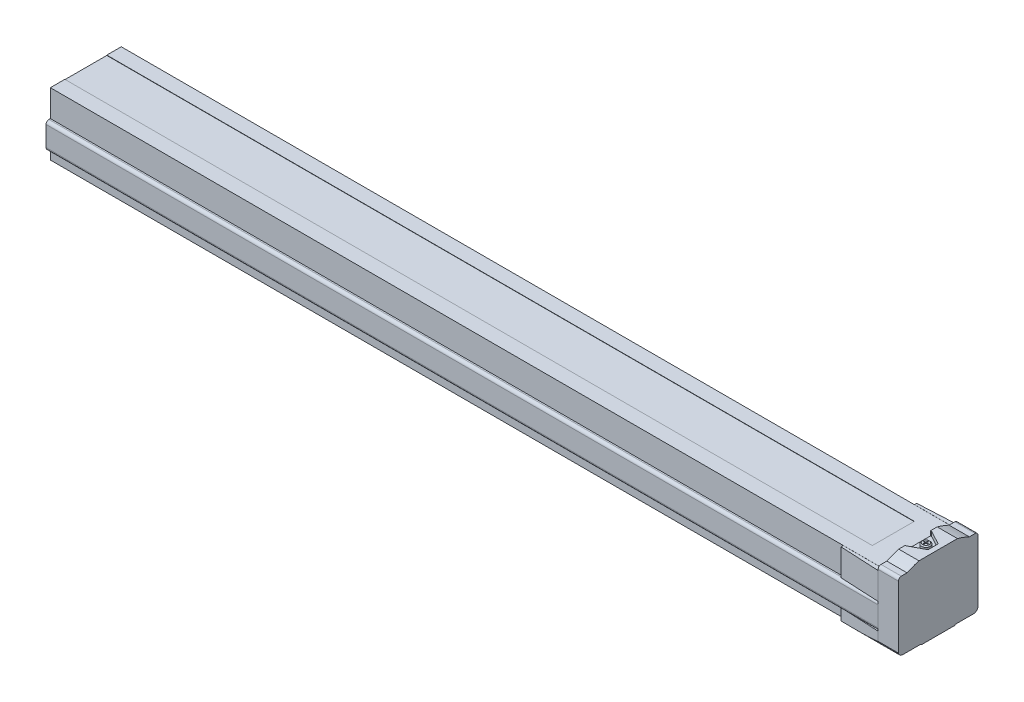
SolidWorks part; units mm, degrees
ref_plane "Front" through (0, 0, 0) normal (0, 0, 1) x (1, 0, 0)
ref_plane "Top" through (0, 0, 0) normal (0, 1, 0) x (1, 0, 0)
ref_plane "Right" through (0, 0, 0) normal (1, 0, 0) x (0, 0, -1)
ref_plane "Plane1" through (0, 0, 0) normal (1, 0, 0) x (0, 0, -1)
sketch "Sketch1" plane through (0, 0, 0) normal (1, 0, 0) x (0, 0, -1)
  line L0 (-28.5, 46) -> (-28.5, 2.9714)
  line L1 (-28.5, 2.9714) -> (-27.5, 2.9714)
  line L2 (-27.5, 2.9714) -> (-27.3284, 2.5)
  line L3 (-24.5, 0.5) -> (-12, 0.5)
  line L4 (-12, 0.5) -> (-11.5, 0)
  line L5 (-11.5, 0) -> (11.5, 0)
  line L6 (11.5, 0) -> (12, 0.5)
  line L7 (12, 0.5) -> (24.5, 0.5)
  line L8 (27.3284, 2.5) -> (27.5, 2.9714)
  line L9 (27.5, 2.9714) -> (28.5, 2.9714)
  line L10 (28.5, 2.9714) -> (28.5, 46)
  line L11 (28.5, 46) -> (27.5, 46)
  line L12 (25.5, 48) -> (21.524, 48)
  line L13 (13.2951, 51.07) -> (-13.2951, 51.07)
  line L14 (-21.524, 48) -> (-25.5, 48)
  line L15 (-27.5, 46) -> (-28.5, 46)
  arc A0 (-27.3284, 2.5) -> (-24.5, 0.5) centre (-24.5, 3.5) ccw
  arc A1 (24.5, 0.5) -> (27.3284, 2.5) centre (24.5, 3.5) ccw
  arc A2 (27.5, 46) -> (25.5, 48) centre (25.5, 46) ccw
  arc A3 (21.524, 48) -> (13.2951, 51.07) centre (0, 2.87) ccw
  arc A4 (-13.2951, 51.07) -> (-21.524, 48) centre (0, 2.87) ccw
  arc A5 (-25.5, 48) -> (-27.5, 46) centre (-25.5, 46) ccw
extrude "Boss-Extrude1" add sketch "Sketch1" along normal blind 930
ref_plane "Plane2" through (916, 0, 0) normal (1, 0, 0) x (0, 0, -1)
sketch "Sketch2" plane through (916, 0, 0) normal (1, 0, 0) x (0, 0, -1)
  line L0 (-92.8608, 99.7478) -> (-92.8608, -68.8998)
  line L1 (-92.8608, -68.8998) -> (111.9255, -68.8998)
  line L2 (111.9255, -68.8998) -> (111.9255, 99.7478)
  line L3 (111.9255, 99.7478) -> (-92.8608, 99.7478)
  line L4 (-27.5, 24.8) -> (-27.5, 11)
  line L5 (-25.5, 9) -> (-24.5, 9)
  line L6 (-24.5, 9) -> (-24.5, 2)
  line L7 (-24.5, 2) -> (-22.5, 0)
  line L8 (-22.5, 0) -> (22.5, 0)
  line L9 (22.5, 0) -> (24.5, 2)
  line L10 (24.5, 2) -> (24.5, 9)
  line L11 (24.5, 9) -> (25.5, 9)
  line L12 (27.5, 11) -> (27.5, 24.8)
  line L13 (25.5, 26.8) -> (24.5, 26.8)
  line L14 (24.5, 26.8) -> (24.5, 45.3)
  line L15 (24.5, 45.3) -> (-24.5, 45.3)
  line L16 (-24.5, 45.3) -> (-24.5, 26.8)
  line L17 (-24.5, 26.8) -> (-25.5, 26.8)
  arc A0 (-27.5, 11) -> (-25.5, 9) centre (-25.5, 11) ccw
  arc A1 (25.5, 9) -> (27.5, 11) centre (25.5, 11) ccw
  arc A2 (27.5, 24.8) -> (25.5, 26.8) centre (25.5, 24.8) ccw
  arc A3 (-25.5, 26.8) -> (-27.5, 24.8) centre (-25.5, 24.8) ccw
extrude "Cut-Extrude1" cut sketch "Sketch2" against normal blind 909.5
ref_plane "Plane3" through (0, 0, 0) normal (1, 0, 0) x (0, 0, -1)
sketch "Sketch3" plane through (0, 0, 0) normal (1, 0, 0) x (0, 0, -1)
  line L0 (-200, 100) -> (-200, -100)
  line L1 (-200, -100) -> (200, -100)
  line L2 (200, -100) -> (200, 100)
  line L3 (200, 100) -> (-200, 100)
  line L4 (-27.5, 46) -> (-27.5, 2.9714)
  line L5 (-27.5, 2.9714) -> (-27.3284, 2.5)
  line L6 (-24.5, 0.5) -> (-12, 0.5)
  line L7 (-12, 0.5) -> (-11.5, 0)
  line L8 (-11.5, 0) -> (11.5, 0)
  line L9 (11.5, 0) -> (12, 0.5)
  line L10 (12, 0.5) -> (24.5, 0.5)
  line L11 (27.3284, 2.5) -> (27.5, 2.9714)
  line L12 (27.5, 2.9714) -> (27.5, 46)
  line L13 (25.5, 48) -> (21.524, 48)
  line L14 (13.2951, 51.07) -> (-13.2951, 51.07)
  line L15 (-21.524, 48) -> (-25.5, 48)
  arc A0 (-27.3284, 2.5) -> (-24.5, 0.5) centre (-24.5, 3.5) ccw
  arc A1 (24.5, 0.5) -> (27.3284, 2.5) centre (24.5, 3.5) ccw
  arc A2 (27.5, 46) -> (25.5, 48) centre (25.5, 46) ccw
  arc A3 (21.524, 48) -> (13.2951, 51.07) centre (0, 2.87) ccw
  arc A4 (-13.2951, 51.07) -> (-21.524, 48) centre (0, 2.87) ccw
  arc A5 (-25.5, 48) -> (-27.5, 46) centre (-25.5, 46) ccw
extrude "Cut-Extrude2" cut sketch "Sketch3" along normal blind 930
ref_plane "Plane4" through (0, 0, 0) normal (1, 0, 0) x (0, 0, -1)
sketch "Sketch4" plane through (0, 0, 0) normal (1, 0, 0) x (0, 0, -1)
  line L0 (-24.5, 30) -> (24.5, 30)
  line L1 (24.5, 30) -> (24.5, 45.3)
  line L2 (24.5, 45.3) -> (24.45, 45.3)
  line L3 (24.45, 45.3) -> (24.5, 45.35)
  line L4 (24.5, 45.35) -> (24.5, 48)
  line L5 (24.5, 48) -> (24, 48)
  line L6 (24, 48) -> (22.2857, 52.7101)
  line L7 (17.5872, 56) -> (-17.0842, 56)
  line L8 (-21.6157, 53.1131) -> (-24, 48)
  line L9 (-24, 48) -> (-24.5, 48)
  line L10 (-24.5, 48) -> (-24.5, 45.35)
  line L11 (-24.5, 45.35) -> (-24.45, 45.3)
  line L12 (-24.45, 45.3) -> (-24.5, 45.3)
  line L13 (-24.5, 45.3) -> (-24.5, 30)
  arc A0 (22.2857, 52.7101) -> (17.5872, 56) centre (17.5872, 51) ccw
  arc A1 (-17.0842, 56) -> (-21.6157, 53.1131) centre (-17.0842, 51) ccw
extrude "Boss-Extrude2" add sketch "Sketch4" along normal blind 127.35
ref_plane "Plane5" through (0, 0, 0) normal (0, 0, 1) x (1, 0, 0)
sketch "Sketch5" plane through (0, 0, 0) normal (0, 0, 1) x (1, 0, 0)
  line L0 (97.35, 71.9713) -> (150, 71.9713)
  line L1 (150, 71.9713) -> (150, 45.3)
  line L2 (150, 45.3) -> (127.35, 45.3)
  line L3 (127.35, 45.3) -> (127.35, 45.79)
  line L4 (126.9005, 47.0533) -> (120.2965, 55.1583)
  line L5 (116.4203, 57) -> (97.35, 57)
  line L6 (97.35, 57) -> (97.35, 71.9713)
  line L7 (97.35, 57) -> (97.35, 71.9713) construction
  arc A0 (127.35, 45.79) -> (126.9005, 47.0533) centre (125.35, 45.79) ccw
  arc A1 (120.2965, 55.1583) -> (116.4203, 57) centre (116.4203, 52) ccw
revolve "Cut-Revolve1" cut sketch "Sketch5" angle 75 about L7 other way angle 75 reverse direction yes
ref_plane "Plane6" through (0, 48, 0) normal (0, 1, 0) x (-1, 0, 0)
sketch "Sketch6" plane through (0, 48, 0) normal (0, 1, 0) x (-1, 0, 0)
  line L0 (-916, 8.7) -> (-916.7202, 8.7)
  line L1 (-916.7202, 8.7) -> (-926.5, 3.5)
  line L2 (-926.5, 3.5) -> (-926.5, -3.5)
  line L3 (-926.5, -3.5) -> (-916.7202, -8.7)
  line L4 (-916.7202, -8.7) -> (-916, -8.7)
  line L5 (-916, -8.7) -> (-916, 8.7)
extrude "Cut-Extrude4" cut sketch "Sketch6" along normal blind 20
ref_plane "Plane7" through (0, 0, 0) normal (0, 0, 1) x (1, 0, 0)
sketch "Sketch7" plane through (0, 0, 0) normal (0, 0, 1) x (1, 0, 0)
  line L0 (921.5, 48) -> (918.5, 48)
  line L1 (918.5, 48) -> (918.5, 50.2929)
  line L2 (918.5, 50.2929) -> (919.2071, 51)
  line L3 (919.2071, 51) -> (921.5, 51)
  line L4 (921.5, 51) -> (921.5, 48)
  line L5 (921.5, 51) -> (921.5, 48) construction
revolve "Revolve1" add sketch "Sketch7" angle 360 about L5 reverse direction yes
ref_plane "Plane8" through (0, 51, 0) normal (0, 1, 0) x (-1, 0, 0)
sketch "Sketch8" plane through (0, 51, 0) normal (0, 1, 0) x (-1, 0, 0)
  line L0 (-923.0716, -0.3) -> (-921.8, -0.3)
  line L1 (-921.8, -0.3) -> (-921.8, -1.5716)
  line L2 (-921.2, -1.5716) -> (-921.2, -0.3)
  line L3 (-921.2, -0.3) -> (-919.9284, -0.3)
  line L4 (-919.9284, 0.3) -> (-921.2, 0.3)
  line L5 (-921.2, 0.3) -> (-921.2, 1.5716)
  line L6 (-921.8, 1.5716) -> (-921.8, 0.3)
  line L7 (-921.8, 0.3) -> (-923.0716, 0.3)
  arc A0 (-923.0716, 0.3) -> (-923.0716, -0.3) centre (-921.5, 0) ccw
  arc A1 (-921.8, -1.5716) -> (-921.2, -1.5716) centre (-921.5, 0) ccw
  arc A2 (-919.9284, -0.3) -> (-919.9284, 0.3) centre (-921.5, 0) ccw
  arc A3 (-921.2, 1.5716) -> (-921.8, 1.5716) centre (-921.5, 0) ccw
extrude "Cut-Extrude5" cut sketch "Sketch8" against normal blind 1
ref_plane "Plane9" through (0, 0, 0) normal (0, 0, 1) x (1, 0, 0)
sketch "Sketch9" plane through (0, 0, 0) normal (0, 0, 1) x (1, 0, 0)
  line L0 (-50, 0.5) -> (-50, 0)
  line L1 (-50, 0) -> (79, 0)
  line L2 (79, 0) -> (78.5, 0.5)
  line L3 (78.5, 0.5) -> (-50, 0.5)
extrude "Cut-Extrude6" cut sketch "Sketch9" against normal blind 20 and the other way blind 20
ref_plane "Plane10" through (0, 0, 0) normal (0, 1, 0) x (-1, 0, 0)
sketch "Sketch10" plane through (0, 0, 0) normal (0, 1, 0) x (-1, 0, 0)
  line L0 (-625.5, 2) -> (-627.5, 2)
  line L1 (-627.5, -2) -> (-625.5, -2)
  arc A0 (-625.5, -2) -> (-625.5, 2) centre (-625.5, 0) ccw
  arc A1 (-627.5, 2) -> (-627.5, -2) centre (-627.5, 0) ccw
extrude "Cut-Extrude7" cut sketch "Sketch10" along normal blind 6
ref_plane "Plane11" through (0, 26.8, 0) normal (0, 1, 0) x (-1, 0, 0)
sketch "Sketch11" plane through (0, 26.8, 0) normal (0, 1, 0) x (-1, 0, 0)
  line L0 (0, 27.5) -> (-6, 27.5)
  line L1 (-6, 27.5) -> (-34, 26.1)
  line L2 (-34, 26.1) -> (-34, -26.1)
  line L3 (-34, -26.1) -> (-6, -27.5)
  line L4 (-6, -27.5) -> (0, -27.5)
  line L5 (0, -27.5) -> (0, 27.5)
extrude "Boss-Extrude8" add sketch "Sketch11" along normal blind 21.2
ref_plane "Plane12" through (0, 0, 0) normal (0, 0, 1) x (1, 0, 0)
sketch "Sketch12" plane through (0, 0, 0) normal (0, 0, 1) x (1, 0, 0)
  line L0 (-20, -15) -> (15, -15)
  line L1 (15, -15) -> (15, 0)
  line L2 (15, 0) -> (5.5878, 0)
  line L3 (0.6068, 4.5642) -> (0, 11.5)
  line L4 (0, 11.5) -> (0, 40.45)
  line L5 (0, 40.45) -> (2.1897, 52.8682)
  line L6 (7.1137, 57) -> (15, 57)
  line L7 (15, 57) -> (15, 60)
  line L8 (15, 60) -> (-20, 60)
  line L9 (-20, 60) -> (-20, -15)
  arc A0 (5.5878, 0) -> (0.6068, 4.5642) centre (5.5878, 5) cw
  arc A1 (2.1897, 52.8682) -> (7.1137, 57) centre (7.1137, 52) cw
extrude "Cut-Extrude9" cut sketch "Sketch12" against normal blind 30 and the other way blind 30
ref_plane "Plane13" through (0, 0, 0) normal (1, 0, 0) x (0, 0, -1)
sketch "Sketch13" plane through (0, 0, 0) normal (1, 0, 0) x (0, 0, -1)
  line L0 (-10, 46.95) -> (-10, 42.95)
  line L1 (-5, 37.95) -> (5, 37.95)
  line L2 (10, 42.95) -> (10, 46.95)
  line L3 (9, 47.95) -> (-9, 47.95)
  arc A0 (-10, 42.95) -> (-5, 37.95) centre (-5, 42.95) ccw
  arc A1 (5, 37.95) -> (10, 42.95) centre (5, 42.95) ccw
  arc A2 (10, 46.95) -> (9, 47.95) centre (9, 46.95) ccw
  arc A3 (-9, 47.95) -> (-10, 46.95) centre (-9, 46.95) ccw
extrude "Cut-Extrude10" cut sketch "Sketch13" against normal blind 2 and the other way blind 2
ref_plane "Plane14" through (2, 0, 0) normal (1, 0, 0) x (0, 0, -1)
sketch "Sketch14" plane through (2, 0, 0) normal (1, 0, 0) x (0, 0, -1)
  circle A0 centre (-3.5, 43.7) radius 3.25
extrude "Boss-Extrude3" add sketch "Sketch14" against normal blind 20
ref_plane "Plane15" through (2, 0, 0) normal (1, 0, 0) x (0, 0, -1)
sketch "Sketch15" plane through (2, 0, 0) normal (1, 0, 0) x (0, 0, -1)
  circle A0 centre (3.5, 43.7) radius 3.25
extrude "Boss-Extrude4" add sketch "Sketch15" against normal blind 20
ref_plane "Plane16" through (0, 9, 0) normal (0, 1, 0) x (-1, 0, 0)
sketch "Sketch16" plane through (0, 9, 0) normal (0, 1, 0) x (-1, 0, 0)
  line L0 (0, 27.5) -> (-6, 27.5)
  line L1 (-6, 27.5) -> (-34, 26.1)
  line L2 (-34, 26.1) -> (-34, -26.1)
  line L3 (-34, -26.1) -> (-6, -27.5)
  line L4 (-6, -27.5) -> (0, -27.5)
  line L5 (0, -27.5) -> (0, 27.5)
extrude "Boss-Extrude5" add sketch "Sketch16" against normal blind 8.56
ref_plane "Plane17" through (0, 0, 0) normal (1, 0, 0) x (0, 0, -1)
sketch "Sketch17" plane through (0, 0, 0) normal (1, 0, 0) x (0, 0, -1)
  line L0 (-109.3927, 115.6666) -> (-109.3927, -79.3609)
  line L1 (-109.3927, -79.3609) -> (125.9854, -79.3609)
  line L2 (125.9854, -79.3609) -> (125.9854, 115.6666)
  line L3 (125.9854, 115.6666) -> (-109.3927, 115.6666)
  line L4 (-27.5, 46) -> (-27.5, 2.9714)
  line L5 (-27.5, 2.9714) -> (-27.3284, 2.5)
  line L6 (-24.5, 0.5) -> (24.5, 0.5)
  line L7 (27.3284, 2.5) -> (27.5, 2.9714)
  line L8 (27.5, 2.9714) -> (27.5, 46)
  line L9 (25.5, 48) -> (24, 48)
  line L10 (24, 48) -> (24, 65)
  line L11 (24, 65) -> (-24, 65)
  line L12 (-24, 65) -> (-24, 48)
  line L13 (-24, 48) -> (-25.5, 48)
  arc A0 (-27.3284, 2.5) -> (-24.5, 0.5) centre (-24.5, 3.5) ccw
  arc A1 (24.5, 0.5) -> (27.3284, 2.5) centre (24.5, 3.5) ccw
  arc A2 (27.5, 46) -> (25.5, 48) centre (25.5, 46) ccw
  arc A3 (-25.5, 48) -> (-27.5, 46) centre (-25.5, 46) ccw
extrude "Cut-Extrude14" cut sketch "Sketch17" along normal blind 40
ref_plane "Plane18" through (0, 26.8, 0) normal (0, 1, 0) x (-1, 0, 0)
sketch "Sketch18" plane through (0, 26.8, 0) normal (0, 1, 0) x (-1, 0, 0)
  line L0 (-889, 26.1) -> (-917, 27.5)
  line L1 (-917, 27.5) -> (-923, 27.5)
  line L2 (-923, 27.5) -> (-923, -27.5)
  line L3 (-923, -27.5) -> (-917, -27.5)
  line L4 (-917, -27.5) -> (-889, -26.1)
  line L5 (-889, -26.1) -> (-889, 26.1)
extrude "Boss-Extrude6" add sketch "Sketch18" along normal blind 18.5
ref_plane "Plane19" through (0, 9, 0) normal (0, 1, 0) x (-1, 0, 0)
sketch "Sketch19" plane through (0, 9, 0) normal (0, 1, 0) x (-1, 0, 0)
  line L0 (-889, 26.1) -> (-917, 27.5)
  line L1 (-917, 27.5) -> (-930, 27.5)
  line L2 (-930, 27.5) -> (-930, -27.5)
  line L3 (-930, -27.5) -> (-917, -27.5)
  line L4 (-917, -27.5) -> (-889, -26.1)
  line L5 (-889, -26.1) -> (-889, 26.1)
extrude "Boss-Extrude7" add sketch "Sketch19" against normal blind 8.56
ref_plane "Plane20" through (930, 0, 0) normal (1, 0, 0) x (0, 0, -1)
sketch "Sketch20" plane through (930, 0, 0) normal (1, 0, 0) x (0, 0, -1)
  line L0 (-109.3927, 115.6666) -> (-109.3927, -79.3609)
  line L1 (-109.3927, -79.3609) -> (125.9854, -79.3609)
  line L2 (125.9854, -79.3609) -> (125.9854, 115.6666)
  line L3 (125.9854, 115.6666) -> (-109.3927, 115.6666)
  line L4 (-27.5, 46) -> (-27.5, 2.9714)
  line L5 (-27.5, 2.9714) -> (-27.3284, 2.5)
  line L6 (-24.5, 0.5) -> (-12, 0.5)
  line L7 (-12, 0.5) -> (-11.5, 0)
  line L8 (-11.5, 0) -> (11.5, 0)
  line L9 (11.5, 0) -> (12, 0.5)
  line L10 (12, 0.5) -> (24.5, 0.5)
  line L11 (27.3284, 2.5) -> (27.5, 2.9714)
  line L12 (27.5, 2.9714) -> (27.5, 46)
  line L13 (25.5, 48) -> (24, 48)
  line L14 (24, 48) -> (24, 65)
  line L15 (24, 65) -> (-24, 65)
  line L16 (-24, 65) -> (-24, 48)
  line L17 (-24, 48) -> (-25.5, 48)
  arc A0 (-27.3284, 2.5) -> (-24.5, 0.5) centre (-24.5, 3.5) ccw
  arc A1 (24.5, 0.5) -> (27.3284, 2.5) centre (24.5, 3.5) ccw
  arc A2 (27.5, 46) -> (25.5, 48) centre (25.5, 46) ccw
  arc A3 (-25.5, 48) -> (-27.5, 46) centre (-25.5, 46) ccw
extrude "Cut-Extrude17" cut sketch "Sketch20" against normal blind 50
ref_plane "Plane21" through (0, 0, 0) normal (0, 0, 1) x (1, 0, 0)
sketch "Sketch21" plane through (0, 0, 0) normal (0, 0, 1) x (1, 0, 0)
  line L0 (111, 60.8331) -> (116, 60.8331)
  line L1 (116, 60.8331) -> (116, 55.5)
  line L2 (116, 55.5) -> (115.7, 55.8)
  line L3 (115.7, 55.8) -> (111, 55.8)
  line L4 (111, 55.8) -> (111, 60.8331)
  line L5 (111, 55.8) -> (111, 60.8331) construction
revolve "Cut-Revolve2" cut sketch "Sketch21" angle 360 about L5 reverse direction yes
ref_plane "Plane22" through (0, 55.8, 0) normal (0, 1, 0) x (-1, 0, 0)
sketch "Sketch22" plane through (0, 55.8, 0) normal (0, 1, 0) x (-1, 0, 0)
  line L0 (-108.042, 0.5) -> (-110.5, 0.5)
  line L1 (-110.5, 0.5) -> (-110.5, 2.958)
  line L2 (-111.5, 2.958) -> (-111.5, 0.5)
  line L3 (-111.5, 0.5) -> (-113.958, 0.5)
  line L4 (-113.958, -0.5) -> (-111.5, -0.5)
  line L5 (-111.5, -0.5) -> (-111.5, -2.958)
  line L6 (-110.5, -2.958) -> (-110.5, -0.5)
  line L7 (-110.5, -0.5) -> (-108.042, -0.5)
  arc A0 (-108.042, -0.5) -> (-108.042, 0.5) centre (-111, 0) ccw
  arc A1 (-110.5, 2.958) -> (-111.5, 2.958) centre (-111, 0) ccw
  arc A2 (-113.958, 0.5) -> (-113.958, -0.5) centre (-111, 0) ccw
  arc A3 (-111.5, -2.958) -> (-110.5, -2.958) centre (-111, 0) ccw
extrude "Cut-Extrude18" cut sketch "Sketch22" against normal blind 3
ref_plane "Plane23" through (0, 45.3, 0) normal (0, 1, 0) x (-1, 0, 0)
sketch "Sketch23" plane through (0, 45.3, 0) normal (0, 1, 0) x (-1, 0, 0)
  line L0 (-157, 14.5) -> (-899, 14.5)
  line L1 (-899, 14.5) -> (-899, -14.5)
  line L2 (-899, -14.5) -> (-157, -14.5)
  line L3 (-157, -14.5) -> (-157, 14.5)
extrude "Cut-Extrude19" cut sketch "Sketch23" against normal blind 0.2
ref_plane "Plane24" through (0, 0, 0) normal (0, 0, 1) x (1, 0, 0)
sketch "Sketch24" plane through (0, 0, 0) normal (0, 0, 1) x (1, 0, 0)
  line L0 (126.5, 0) -> (124.5, 0)
  line L1 (124.5, 0) -> (124.5, 6)
  line L2 (124.5, 6) -> (126.5, 7.1547)
  line L3 (126.5, 7.1547) -> (126.5, 0)
  line L4 (126.5, 7.1547) -> (126.5, 0) construction
revolve "Cut-Revolve3" cut sketch "Sketch24" angle 360 about L4 reverse direction yes
ref_plane "Plane25" through (101.5, 0, 0) normal (1, 0, 0) x (0, 0, -1)
sketch "Sketch25" plane through (101.5, 0, 0) normal (1, 0, 0) x (0, 0, -1)
  line L0 (0, 11.0194) -> (2.4585, 9.6)
  line L1 (2.4585, 9.6) -> (2.4585, 0.5415)
  line L2 (2.4585, 0.5415) -> (3, 0)
  line L3 (3, 0) -> (0, 0)
  line L4 (0, 0) -> (0, 11.0194)
  line L5 (0, 0) -> (0, 11.0194) construction
revolve "Cut-Revolve4" cut sketch "Sketch25" angle 360 about L5 reverse direction yes
ref_plane "Plane26" through (901.5, 0, 0) normal (1, 0, 0) x (0, 0, -1)
sketch "Sketch26" plane through (901.5, 0, 0) normal (1, 0, 0) x (0, 0, -1)
  line L0 (0, 11.0194) -> (2.4585, 9.6)
  line L1 (2.4585, 9.6) -> (2.4585, 0.5415)
  line L2 (2.4585, 0.5415) -> (3, 0)
  line L3 (3, 0) -> (0, 0)
  line L4 (0, 0) -> (0, 11.0194)
  line L5 (0, 0) -> (0, 11.0194) construction
revolve "Cut-Revolve5" cut sketch "Sketch26" angle 360 about L5 reverse direction yes
ref_plane "Plane27" through (851.5, 0, 0) normal (1, 0, 0) x (0, 0, -1)
sketch "Sketch27" plane through (851.5, 0, 0) normal (1, 0, 0) x (0, 0, -1)
  line L0 (0, 11.0194) -> (2.4585, 9.6)
  line L1 (2.4585, 9.6) -> (2.4585, 0.5415)
  line L2 (2.4585, 0.5415) -> (3, 0)
  line L3 (3, 0) -> (0, 0)
  line L4 (0, 0) -> (0, 11.0194)
  line L5 (0, 0) -> (0, 11.0194) construction
revolve "Cut-Revolve6" cut sketch "Sketch27" angle 360 about L5 reverse direction yes
ref_plane "Plane28" through (801.5, 0, 0) normal (1, 0, 0) x (0, 0, -1)
sketch "Sketch28" plane through (801.5, 0, 0) normal (1, 0, 0) x (0, 0, -1)
  line L0 (0, 11.0194) -> (2.4585, 9.6)
  line L1 (2.4585, 9.6) -> (2.4585, 0.5415)
  line L2 (2.4585, 0.5415) -> (3, 0)
  line L3 (3, 0) -> (0, 0)
  line L4 (0, 0) -> (0, 11.0194)
  line L5 (0, 0) -> (0, 11.0194) construction
revolve "Cut-Revolve7" cut sketch "Sketch28" angle 360 about L5 reverse direction yes
ref_plane "Plane29" through (751.5, 0, 0) normal (1, 0, 0) x (0, 0, -1)
sketch "Sketch29" plane through (751.5, 0, 0) normal (1, 0, 0) x (0, 0, -1)
  line L0 (0, 11.0194) -> (2.4585, 9.6)
  line L1 (2.4585, 9.6) -> (2.4585, 0.5415)
  line L2 (2.4585, 0.5415) -> (3, 0)
  line L3 (3, 0) -> (0, 0)
  line L4 (0, 0) -> (0, 11.0194)
  line L5 (0, 0) -> (0, 11.0194) construction
revolve "Cut-Revolve8" cut sketch "Sketch29" angle 360 about L5 reverse direction yes
ref_plane "Plane30" through (701.5, 0, 0) normal (1, 0, 0) x (0, 0, -1)
sketch "Sketch30" plane through (701.5, 0, 0) normal (1, 0, 0) x (0, 0, -1)
  line L0 (0, 11.0194) -> (2.4585, 9.6)
  line L1 (2.4585, 9.6) -> (2.4585, 0.5415)
  line L2 (2.4585, 0.5415) -> (3, 0)
  line L3 (3, 0) -> (0, 0)
  line L4 (0, 0) -> (0, 11.0194)
  line L5 (0, 0) -> (0, 11.0194) construction
revolve "Cut-Revolve9" cut sketch "Sketch30" angle 360 about L5 reverse direction yes
ref_plane "Plane31" through (651.5, 0, 0) normal (1, 0, 0) x (0, 0, -1)
sketch "Sketch31" plane through (651.5, 0, 0) normal (1, 0, 0) x (0, 0, -1)
  line L0 (0, 11.0194) -> (2.4585, 9.6)
  line L1 (2.4585, 9.6) -> (2.4585, 0.5415)
  line L2 (2.4585, 0.5415) -> (3, 0)
  line L3 (3, 0) -> (0, 0)
  line L4 (0, 0) -> (0, 11.0194)
  line L5 (0, 0) -> (0, 11.0194) construction
revolve "Cut-Revolve10" cut sketch "Sketch31" angle 360 about L5 reverse direction yes
ref_plane "Plane32" through (601.5, 0, 0) normal (1, 0, 0) x (0, 0, -1)
sketch "Sketch32" plane through (601.5, 0, 0) normal (1, 0, 0) x (0, 0, -1)
  line L0 (0, 11.0194) -> (2.4585, 9.6)
  line L1 (2.4585, 9.6) -> (2.4585, 0.5415)
  line L2 (2.4585, 0.5415) -> (3, 0)
  line L3 (3, 0) -> (0, 0)
  line L4 (0, 0) -> (0, 11.0194)
  line L5 (0, 0) -> (0, 11.0194) construction
revolve "Cut-Revolve11" cut sketch "Sketch32" angle 360 about L5 reverse direction yes
ref_plane "Plane33" through (551.5, 0, 0) normal (1, 0, 0) x (0, 0, -1)
sketch "Sketch33" plane through (551.5, 0, 0) normal (1, 0, 0) x (0, 0, -1)
  line L0 (0, 11.0194) -> (2.4585, 9.6)
  line L1 (2.4585, 9.6) -> (2.4585, 0.5415)
  line L2 (2.4585, 0.5415) -> (3, 0)
  line L3 (3, 0) -> (0, 0)
  line L4 (0, 0) -> (0, 11.0194)
  line L5 (0, 0) -> (0, 11.0194) construction
revolve "Cut-Revolve12" cut sketch "Sketch33" angle 360 about L5 reverse direction yes
ref_plane "Plane34" through (501.5, 0, 0) normal (1, 0, 0) x (0, 0, -1)
sketch "Sketch34" plane through (501.5, 0, 0) normal (1, 0, 0) x (0, 0, -1)
  line L0 (0, 11.0194) -> (2.4585, 9.6)
  line L1 (2.4585, 9.6) -> (2.4585, 0.5415)
  line L2 (2.4585, 0.5415) -> (3, 0)
  line L3 (3, 0) -> (0, 0)
  line L4 (0, 0) -> (0, 11.0194)
  line L5 (0, 0) -> (0, 11.0194) construction
revolve "Cut-Revolve13" cut sketch "Sketch34" angle 360 about L5 reverse direction yes
ref_plane "Plane35" through (451.5, 0, 0) normal (1, 0, 0) x (0, 0, -1)
sketch "Sketch35" plane through (451.5, 0, 0) normal (1, 0, 0) x (0, 0, -1)
  line L0 (0, 11.0194) -> (2.4585, 9.6)
  line L1 (2.4585, 9.6) -> (2.4585, 0.5415)
  line L2 (2.4585, 0.5415) -> (3, 0)
  line L3 (3, 0) -> (0, 0)
  line L4 (0, 0) -> (0, 11.0194)
  line L5 (0, 0) -> (0, 11.0194) construction
revolve "Cut-Revolve14" cut sketch "Sketch35" angle 360 about L5 reverse direction yes
ref_plane "Plane36" through (401.5, 0, 0) normal (1, 0, 0) x (0, 0, -1)
sketch "Sketch36" plane through (401.5, 0, 0) normal (1, 0, 0) x (0, 0, -1)
  line L0 (0, 11.0194) -> (2.4585, 9.6)
  line L1 (2.4585, 9.6) -> (2.4585, 0.5415)
  line L2 (2.4585, 0.5415) -> (3, 0)
  line L3 (3, 0) -> (0, 0)
  line L4 (0, 0) -> (0, 11.0194)
  line L5 (0, 0) -> (0, 11.0194) construction
revolve "Cut-Revolve15" cut sketch "Sketch36" angle 360 about L5 reverse direction yes
ref_plane "Plane37" through (351.5, 0, 0) normal (1, 0, 0) x (0, 0, -1)
sketch "Sketch37" plane through (351.5, 0, 0) normal (1, 0, 0) x (0, 0, -1)
  line L0 (0, 11.0194) -> (2.4585, 9.6)
  line L1 (2.4585, 9.6) -> (2.4585, 0.5415)
  line L2 (2.4585, 0.5415) -> (3, 0)
  line L3 (3, 0) -> (0, 0)
  line L4 (0, 0) -> (0, 11.0194)
  line L5 (0, 0) -> (0, 11.0194) construction
revolve "Cut-Revolve16" cut sketch "Sketch37" angle 360 about L5 reverse direction yes
ref_plane "Plane38" through (301.5, 0, 0) normal (1, 0, 0) x (0, 0, -1)
sketch "Sketch38" plane through (301.5, 0, 0) normal (1, 0, 0) x (0, 0, -1)
  line L0 (0, 11.0194) -> (2.4585, 9.6)
  line L1 (2.4585, 9.6) -> (2.4585, 0.5415)
  line L2 (2.4585, 0.5415) -> (3, 0)
  line L3 (3, 0) -> (0, 0)
  line L4 (0, 0) -> (0, 11.0194)
  line L5 (0, 0) -> (0, 11.0194) construction
revolve "Cut-Revolve17" cut sketch "Sketch38" angle 360 about L5 reverse direction yes
ref_plane "Plane39" through (251.5, 0, 0) normal (1, 0, 0) x (0, 0, -1)
sketch "Sketch39" plane through (251.5, 0, 0) normal (1, 0, 0) x (0, 0, -1)
  line L0 (0, 11.0194) -> (2.4585, 9.6)
  line L1 (2.4585, 9.6) -> (2.4585, 0.5415)
  line L2 (2.4585, 0.5415) -> (3, 0)
  line L3 (3, 0) -> (0, 0)
  line L4 (0, 0) -> (0, 11.0194)
  line L5 (0, 0) -> (0, 11.0194) construction
revolve "Cut-Revolve18" cut sketch "Sketch39" angle 360 about L5 reverse direction yes
ref_plane "Plane40" through (201.5, 0, 0) normal (1, 0, 0) x (0, 0, -1)
sketch "Sketch40" plane through (201.5, 0, 0) normal (1, 0, 0) x (0, 0, -1)
  line L0 (0, 11.0194) -> (2.4585, 9.6)
  line L1 (2.4585, 9.6) -> (2.4585, 0.5415)
  line L2 (2.4585, 0.5415) -> (3, 0)
  line L3 (3, 0) -> (0, 0)
  line L4 (0, 0) -> (0, 11.0194)
  line L5 (0, 0) -> (0, 11.0194) construction
revolve "Cut-Revolve19" cut sketch "Sketch40" angle 360 about L5 reverse direction yes
ref_plane "Plane41" through (151.5, 0, 0) normal (1, 0, 0) x (0, 0, -1)
sketch "Sketch41" plane through (151.5, 0, 0) normal (1, 0, 0) x (0, 0, -1)
  line L0 (0, 11.0194) -> (2.4585, 9.6)
  line L1 (2.4585, 9.6) -> (2.4585, 0.5415)
  line L2 (2.4585, 0.5415) -> (3, 0)
  line L3 (3, 0) -> (0, 0)
  line L4 (0, 0) -> (0, 11.0194)
  line L5 (0, 0) -> (0, 11.0194) construction
revolve "Cut-Revolve20" cut sketch "Sketch41" angle 360 about L5 reverse direction yes
ref_plane "Plane42" through (0, 0, 0) normal (0, 0, 1) x (1, 0, 0)
sketch "Sketch42" plane through (0, 0, 0) normal (0, 0, 1) x (1, 0, 0)
  line L0 (34, 0.5) -> (34.05, 0.5)
  line L1 (34.05, 0.5) -> (34, 0.55)
  line L2 (34, 0.55) -> (34, 0.5)
extrude "Cut-Extrude20" cut sketch "Sketch42" against normal blind 25 and the other way blind 25
ref_plane "Plane43" through (0, 26.8, 0) normal (0, 1, 0) x (-1, 0, 0)
sketch "Sketch43" plane through (0, 26.8, 0) normal (0, 1, 0) x (-1, 0, 0)
  line L0 (-6.5, 27.5) -> (-6.55, 27.5)
  line L1 (-6.55, 27.5) -> (-6.5, 27.45)
  line L2 (-6.5, 27.45) -> (-6.5, 27.5)
extrude "Cut-Extrude21" cut sketch "Sketch43" against normal blind 16
ref_plane "Plane44" through (0, 26.8, 0) normal (0, 1, 0) x (-1, 0, 0)
sketch "Sketch44" plane through (0, 26.8, 0) normal (0, 1, 0) x (-1, 0, 0)
  line L0 (-6.5, -27.5) -> (-6.5, -27.45)
  line L1 (-6.5, -27.45) -> (-6.55, -27.5)
  line L2 (-6.55, -27.5) -> (-6.5, -27.5)
extrude "Cut-Extrude22" cut sketch "Sketch44" against normal blind 16
ref_plane "Plane45" through (916, 0, 0) normal (1, 0, 0) x (0, 0, -1)
sketch "Sketch45" plane through (916, 0, 0) normal (1, 0, 0) x (0, 0, -1)
  line L0 (-24.558, 45.3) -> (-24.5, 45.25)
  line L1 (-24.5, 45.25) -> (-24.5, 45.3)
  line L2 (-24.5, 45.3) -> (-24.558, 45.3)
extrude "Cut-Extrude23" cut sketch "Sketch45" against normal blind 34
ref_plane "Plane46" through (916, 0, 0) normal (1, 0, 0) x (0, 0, -1)
sketch "Sketch46" plane through (916, 0, 0) normal (1, 0, 0) x (0, 0, -1)
  line L0 (24.5, 45.25) -> (24.558, 45.3)
  line L1 (24.558, 45.3) -> (24.5, 45.3)
  line L2 (24.5, 45.3) -> (24.5, 45.25)
extrude "Cut-Extrude24" cut sketch "Sketch46" against normal blind 34
ref_plane "Plane47" through (0, 26.8, 0) normal (0, 1, 0) x (-1, 0, 0)
sketch "Sketch47" plane through (0, 26.8, 0) normal (0, 1, 0) x (-1, 0, 0)
  line L0 (-915.95, 27.5) -> (-916, 27.5)
  line L1 (-916, 27.5) -> (-916, 27.45)
  line L2 (-916, 27.45) -> (-915.95, 27.5)
extrude "Cut-Extrude25" cut sketch "Sketch47" against normal blind 16
ref_plane "Plane48" through (0, 26.8, 0) normal (0, 1, 0) x (-1, 0, 0)
sketch "Sketch48" plane through (0, 26.8, 0) normal (0, 1, 0) x (-1, 0, 0)
  line L0 (-915.95, -27.5) -> (-916, -27.45)
  line L1 (-916, -27.45) -> (-916, -27.5)
  line L2 (-916, -27.5) -> (-915.95, -27.5)
extrude "Cut-Extrude26" cut sketch "Sketch48" against normal blind 16
ref_plane "Plane49" through (0, 0, 24.5) normal (0, 0, 1) x (1, 0, 0)
sketch "Sketch49" plane through (0, 0, 24.5) normal (0, 0, 1) x (1, 0, 0)
  line L0 (888.95, 0.5) -> (889, 0.5)
  line L1 (889, 0.5) -> (889, 0.55)
  line L2 (889, 0.55) -> (888.95, 0.5)
extrude "Cut-Extrude27" cut sketch "Sketch49" against normal blind 12.5
ref_plane "Plane50" through (0, 0, -24.5) normal (0, 0, 1) x (1, 0, 0)
sketch "Sketch50" plane through (0, 0, -24.5) normal (0, 0, 1) x (1, 0, 0)
  line L0 (888.95, 0.5) -> (889, 0.5)
  line L1 (889, 0.5) -> (889, 0.55)
  line L2 (889, 0.55) -> (888.95, 0.5)
extrude "Cut-Extrude28" cut sketch "Sketch50" along normal blind 12.5
sketch "Эскиз1" plane through (930, 0, 0) normal (1, 0, 0) x (0, 0, -1)
  line L1 (-91.3548, 96.9176) -> (94.0128, 96.9176)
  line L2 (-91.3548, 96.9176) -> (-91.3548, -29.7998)
  line L3 (-91.3548, -29.7998) -> (94.0128, -29.7998)
  line L4 (94.0128, 96.9176) -> (94.0128, -29.7998)
sketch "Эскиз2" plane through (0, 0, 0) normal (-1, 0, 0) x (0, 0, 1)
  line L2 (91.8801, -37.3086) -> (-81.4129, -37.3086)
  line L3 (91.8801, -37.3086) -> (91.8801, 79.5518)
  line L4 (91.8801, 79.5518) -> (-81.4129, 79.5518)
  line L5 (-81.4129, -37.3086) -> (-81.4129, 79.5518)
extrude "Вырез-Вытянуть1" cut sketch "Эскиз2" against normal blind 341 and the other way blind 341
